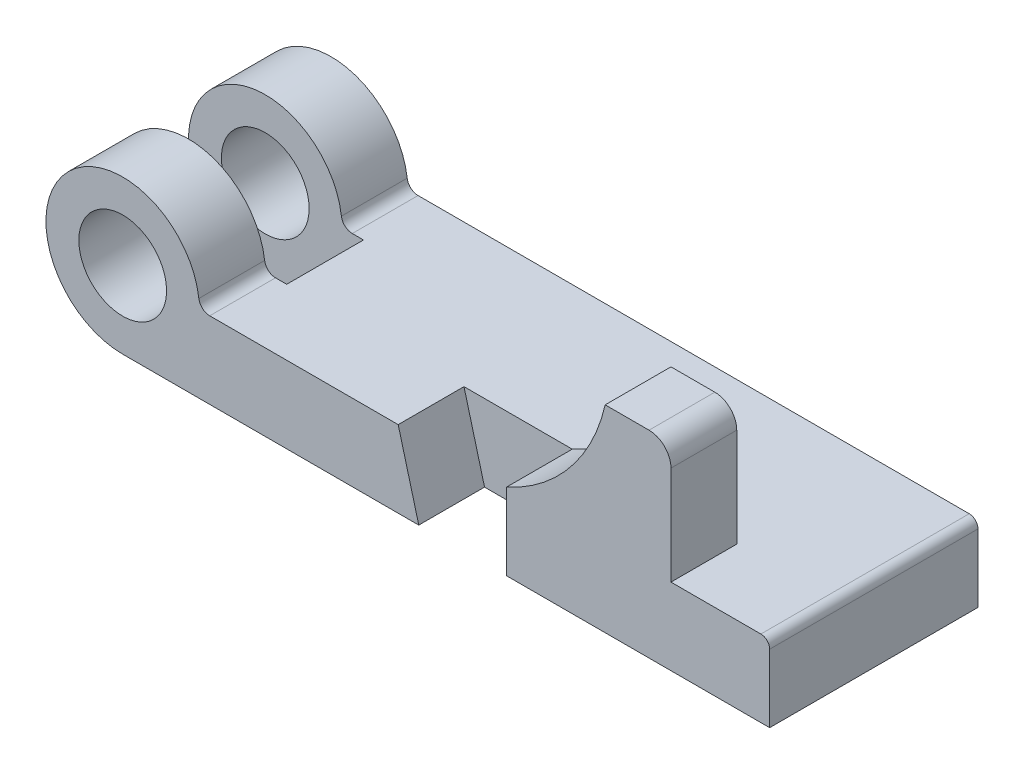
SolidWorks part; units mm, degrees
ref_plane "Front Plane" through (0, 0, 0) normal (0, 0, 1) x (1, 0, 0)
ref_plane "Top Plane" through (0, 0, 0) normal (0, 1, 0) x (1, 0, 0)
ref_plane "Right Plane" through (0, 0, 0) normal (1, 0, 0) x (0, 0, -1)
sketch "Sketch1" plane through (0, 0, 0) normal (0, 0, 1) x (1, 0, 0)
  line L0 (0, -22.225) -> (85.725, -22.225)
  line L1 (85.725, -22.225) -> (79.7698, 0)
  line L2 (79.7698, 0) -> (111.125, 0)
  line L3 (111.125, 0) -> (111.125, -22.225)
  line L4 (111.125, -22.225) -> (187.325, -22.225)
  line L5 (187.325, -22.225) -> (187.325, -2.54)
  line L6 (184.785, 0) -> (158.75, 0)
  line L7 (158.75, 0) -> (158.75, 28.575)
  line L8 (152.4, 34.925) -> (139.7, 34.925)
  line L9 (25.2008, 0) -> (28.4434, 0)
  line L10 (28.4434, 0) -> (41.275, -22.225)
  line L11 (79.7698, 0) -> (28.4434, 0)
  line L12 (85.725, -22.225) -> (111.125, -22.225)
  line L13 (111.125, 0) -> (158.75, 0)
  circle A0 centre (0, 0) radius 12.7
  circle A1 centre (0, 0) radius 22.225
  arc A2 (111.125, 0) -> (139.7, 34.925) centre (90.1862, 46.284) ccw
  arc A3 (187.325, -2.54) -> (184.785, 0) centre (184.785, -2.54) ccw
  arc A4 (22.0507, 2.7781) -> (25.2008, 0) centre (25.2008, 3.175) ccw
  arc A5 (158.75, 28.575) -> (152.4, 34.925) centre (152.4, 28.575) ccw
  point P20 (187.325, 0)
  point P25 (158.75, 34.925)
  dimension "D1" = 44.45
  dimension "D2" = 25.4
  dimension "D13" = 57.15
  dimension "D14" = 101.6
  dimension "D15" = 2.54
  dimension "D16" = 6.35
  dimension "D17" = 6.35
  dimension "D3" = 85.725
  dimension "D4" = 60
  dimension "D5" = 41.275
  dimension "D6" = 75
  dimension "D7" = 22.225
  dimension "D8" = 25.4
  dimension "D9" = 187.325
  dimension "D10" = 22.225
  dimension "D11" = 28.575
  dimension "D12" = 19.05
extrude "Boss-Extrude1" add sketch "Sketch1" along normal mid plane 22.225 contours L1 L11 L10 L0 | L1 L12 L3 L2 | L5 A3 L6 L7 L8 A2 L3 L4 region at (58.6909, -10.8466, 0) region at (96.8841, -10.7238, 0) region at (149.1943, -11.1211, 0)
extrude "Boss-Extrude2" add sketch "Sketch1<4>" along normal blind 19.05 from vertex contours A1 A0 | A4 A1 L0 L10 L9 | L1 L11 L10 L0 | L5 A3 L6 L7 L8 A2 L3 L4 | A2 L13 L7 L8 region at (25.8311, -14.0957, 0) region at (-16.1973, 14.2847, 0) region at (58.6909, -10.8466, 0) region at (149.1943, -11.1211, 0) region at (143.1817, 14.6209, 0) starting at point (28.4434, 0, 11.1125)
sketch "Sketch1<4>" plane through (0, 0, 0) normal (0, 0, 1) x (1, 0, 0) same geometry as "Sketch1"
extrude "Boss-Extrude4" add sketch "Sketch1<6>" against normal blind 19.05 from vertex contours A1 A0 | A4 A1 L0 L10 L9 | L1 L11 L10 L0 | L5 A3 L6 L13 L3 L4 | L1 L12 L3 L2 region at (25.8311, -14.0957, 0) region at (-16.1973, 14.2847, 0) region at (58.6909, -10.8466, 0) region at (96.8841, -10.7238, 0) region at (149.1943, -11.1211, 0) starting at point (28.4434, 0, -11.1125)
sketch "Sketch1<6>" plane through (0, 0, 0) normal (0, 0, 1) x (1, 0, 0) same geometry as "Sketch1"
